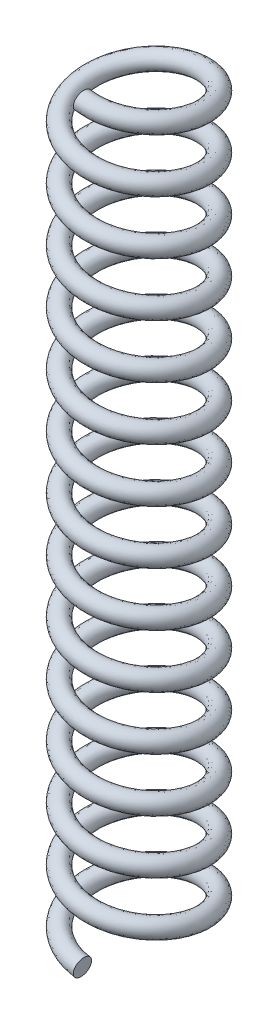
SolidWorks part; units mm, degrees
ref_plane "Front Plane" through (0, 0, 0) normal (0, 0, 1) x (1, 0, 0)
ref_plane "Top Plane" through (0, 0, 0) normal (0, 1, 0) x (1, 0, 0)
ref_plane "Right Plane" through (0, 0, 0) normal (1, 0, 0) x (0, 0, -1)
other "Configuration Table"
sketch "Sketch1" plane through (0, 0, 0) normal (0, 1, 0) x (1, 0, 0)
  circle A0 centre (0, 0) radius 2.5
curve "Coil_Helix" pitch 2.3714 height 33.1999 turns 14
sweep "Coil_Wire" add path "Coil_Helix" circular profile diameter 0.8 parameters "D3"=0.8
